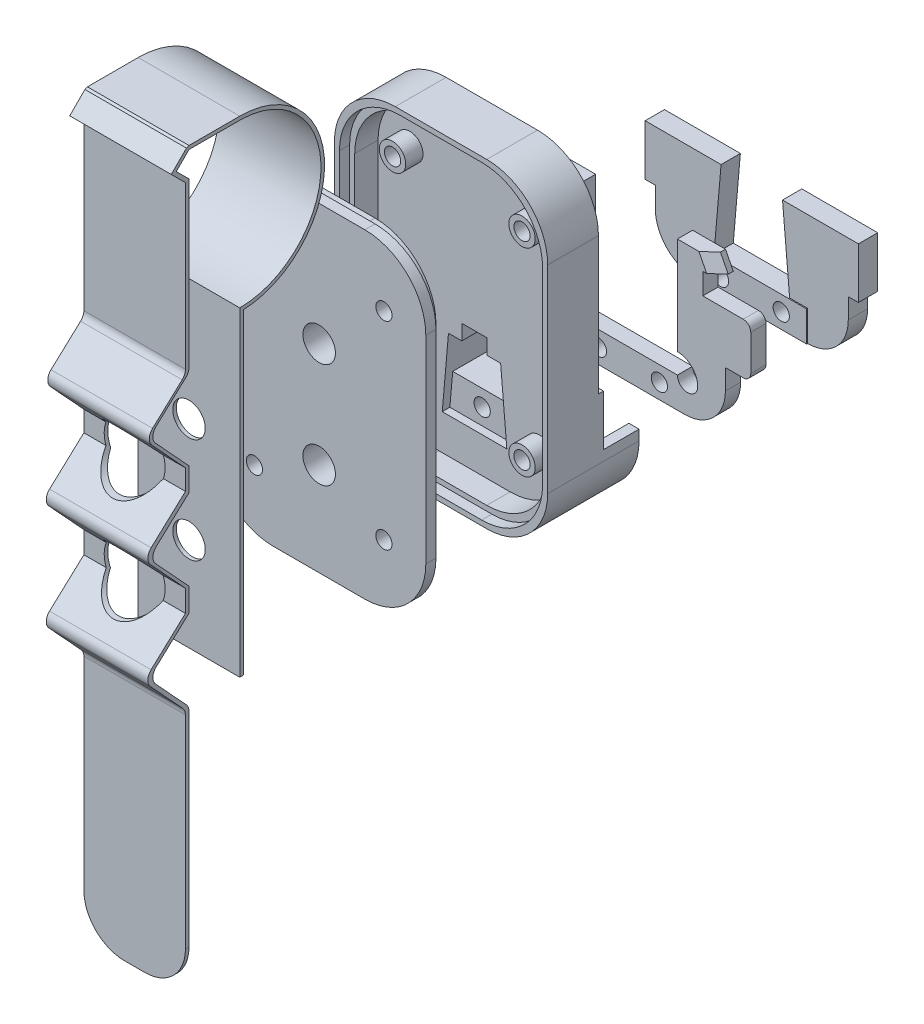
SolidWorks part; units mm, degrees
ref_plane "前视基准面" through (0, 0, 0) normal (0, 0, 1) x (1, 0, 0)
ref_plane "上视基准面" through (0, 0, 0) normal (0, 1, 0) x (1, 0, 0)
ref_plane "右视基准面" through (0, 0, 0) normal (1, 0, 0) x (0, 0, -1)
sketch "草图2" plane through (0, 0, 0) normal (0, 0, 1) x (1, 0, 0)
  line L1 (-21, 31.5) -> (21, 31.5)
  line L2 (-21, 31.5) -> (-21, -31.5)
  line L3 (-21, -31.5) -> (21, -31.5)
  line L4 (21, 31.5) -> (21, -31.5)
  line L5 (-21, 31.5) -> (21, -31.5) construction
  line L6 (-21, -31.5) -> (21, 31.5) construction
  point P0 (0, 0)
extrude "凸台-拉伸1" add sketch "草图2" along normal blind 10
sketch "草图3" plane through (0, 0, 0) normal (0, 0, -1) x (-1, 0, 0)
  line L0 (21, 31.5) -> (21, -31.5) construction
  line L1 (-21, -31.5) -> (21, -31.5)
  line L2 (-21, -31.5) -> (-21, -7.5)
  line L3 (-21, -7.5) -> (21, -7.5)
  line L4 (21, -31.5) -> (21, -7.5)
extrude "凸台-拉伸2" add sketch "草图3" along normal blind 8
sketch "草图4" plane through (0, -7.5, 0) normal (0, 1, 0) x (1, 0, 0)
  line L0 (0, 0) -> (0, 3)
  line L1 (0, 3) -> (5.5, 3)
  line L2 (0, 3) -> (-5.5, 3)
  line L3 (5.5, 3) -> (3.5, 0)
  line L4 (21, 0) -> (-21, 0) construction
  line L5 (-5.5, 3) -> (-3.5, 0)
  line L6 (0, 0) -> (3.5, 0)
  line L7 (0, 0) -> (-3.5, 0)
  line M4 (-21, 0) -> (21, 0)
  dimension "D1" = 3
extrude "凸台-拉伸3" add sketch "草图4" along normal blind 32 contours L2 L5 L0 M4 | L3 L1 L0 M4 region at (-2.287, -7.5, -1.6111) region at (2.287, -7.5, -1.6111)
sketch "草图5" plane through (0, -7.5, 0) normal (0, 1, 0) x (1, 0, 0)
  line L0 (0, 6.25) -> (0, 0)
  line L1 (-3.81, 6.25) -> (3.81, 6.25)
  line L3 (-5.05, 5) -> (5.05, 5)
  line L4 (-5.05, 5) -> (-5.05, 7.5)
  line L5 (-5.05, 7.5) -> (5.05, 7.5)
  line L6 (5.05, 5) -> (5.05, 7.5)
  line L7 (-5.05, 5) -> (5.05, 7.5) construction
  line L8 (-5.05, 7.5) -> (5.05, 5) construction
  circle A0 centre (1.27, 6.25) radius 0.74
  circle A1 centre (3.81, 6.25) radius 0.74
  circle A2 centre (-1.27, 6.25) radius 0.74
  circle A3 centre (-3.81, 6.25) radius 0.74
  point P2 (0, 6.25)
  point P5 (0, 6.25)
  dimension "D4" = 1.48
  dimension "D2" = 10.1
  dimension "D5" = 2
  dimension "D6" = 3
extrude "切除-拉伸1" cut sketch "草图5" against normal blind 10 contours A3 | A2 | A0 | A1 | A2 | A0 region at (-4.5291, -7.5, -6.25) region at (-1.27, -7.5, -5.9359) region at (3.81, -7.5, -6.9691) region at (1.27, -7.5, -5.9359)
fillet "圆角1" radius 3 2 edges at (-4.5, 24.5, -1.5) (4.5, 24.5, -1.5)
sketch "草图6" plane through (0, 0, -8) normal (0, 0, -1) x (-1, 0, 0)
  line L0 (-21, -7.5) -> (-17.55, -7.5)
  line L1 (-3.5, -7.5) -> (-21, -7.5) construction
  line L2 (21, -7.5) -> (17.55, -7.5)
  line L3 (21, -7.5) -> (3.5, -7.5) construction
  line L4 (-17.55, -7.5) -> (-14.55, -7.5)
  line L5 (17.55, -7.5) -> (14.55, -7.5)
  line L6 (21, -7.5) -> (-21, -7.5) construction
  line L7 (-14.55, -7.5) -> (-9.55, -7.5)
  line L8 (14.55, -7.5) -> (9.55, -7.5)
  line L9 (-9.55, -7.5) -> (-7.55, -7.5)
  line L10 (9.55, -7.5) -> (7.55, -7.5)
  line L11 (-21, -31.5) -> (21, -31.5) construction
  line L12 (-21, -7.5) -> (-9.55, -7.5)
  line L13 (-21, -7.5) -> (-21, -17.5)
  line L15 (-9.55, -7.5) -> (-9.55, -19.5)
  line L16 (-21, -17.5) -> (-19, -17.5)
  line L17 (-21, -17.5) -> (-21, -31.5)
  line L19 (-19, -17.5) -> (-19, -21.5)
  line L20 (-21, -17.5) -> (-21, -7.5)
  line L22 (-9.55, -31.5) -> (-9.55, -29.5)
  line L23 (-9.55, -29.5) -> (-11, -29.5)
  line L25 (-9.55, -29.5) -> (0, -29.5)
  line L27 (-9.55, -23.5) -> (0, -23.5)
  line L29 (9.55, -29.5) -> (11, -29.5)
  line L30 (0, -23.5) -> (9.55, -23.5)
  line L32 (0, -29.5) -> (9.55, -29.5)
  line L34 (19, -21.5) -> (19, -17.5)
  line L35 (21, -31.5) -> (21, -7.5) construction
  line L36 (19, -17.5) -> (21, -17.5)
  line L37 (9.55, -19.5) -> (9.55, -7.5)
  line L38 (9.55, -29.5) -> (9.55, -31.5)
  line L39 (21, -7.5) -> (21, -17.5)
  line L40 (-21, -7.5) -> (-21, -17.5)
  arc A0 (-11, -29.5) -> (-19, -21.5) centre (-11, -21.5) cw
  arc A1 (-9.55, -19.5) -> (-13.55, -23.5) centre (-9.55, -23.5) ccw
  arc A2 (-13.55, -23.5) -> (-9.55, -23.5) centre (-11.55, -23.5) ccw
  arc A3 (11, -29.5) -> (19, -21.5) centre (11, -21.5) ccw
  arc A4 (9.55, -23.5) -> (13.55, -23.5) centre (11.55, -23.5) ccw
  arc A5 (13.55, -23.5) -> (9.55, -19.5) centre (9.55, -23.5) ccw
  line M7 (-21, -7.5) -> (-21, -31.5)
  line M9 (21, -31.5) -> (21, -7.5)
  line M10 (21, -7.5) -> (-21, -7.5)
  dimension "D7" = 8
  dimension "D8" = 2
  dimension "D9" = 2
  dimension "D10" = 2
  dimension "D11" = 4
  dimension "D12" = 4
  dimension "D13" = 10
  dimension "D1" = 3.45
  dimension "D2" = 3
  dimension "D3" = 5
  dimension "D4" = 2
  dimension "D5" = 2
  dimension "D6" = 2
  dimension "D14" = 10
extrude "切除-拉伸2" cut sketch "草图6" against normal blind 7 contours A5 A4 L30 L27 A2 A1 L15 L16 L19 A0 L23 L25 L32 L29 A3 L34 L36 L37 M10 M7 M9 region at (19.275, -7.9741, -8)
sketch "草图7" plane through (0, 0, -8) normal (0, 0, -1) x (-1, 0, 0)
  line L0 (-9.55, -7.5) -> (-7.55, -7.5)
  line L1 (9.55, -7.5) -> (-9.55, -7.5) construction
  line L2 (9.55, -7.5) -> (7.55, -7.5)
  line L4 (-7.55, -7.5) -> (-13.55, -7.5)
  line L5 (-7.55, -7.5) -> (-7.55, -25.5)
  line L6 (-7.55, -25.5) -> (-13.55, -25.5)
  line L7 (-13.55, -7.5) -> (-13.55, -25.5)
  line L8 (7.55, -7.5) -> (13.55, -7.5)
  line L9 (7.55, -7.5) -> (7.55, -25.5)
  line L10 (7.55, -25.5) -> (13.55, -25.5)
  line L11 (13.55, -7.5) -> (13.55, -25.5)
  line M3 (9.55, -19.5) -> (9.55, -7.5)
  line M4 (9.55, -7.5) -> (-9.55, -7.5)
  line M5 (-9.55, -7.5) -> (-9.55, -19.5)
  arc M6 (-9.55, -19.5) -> (-13.55, -23.5) centre (-9.55, -23.5) ccw
  arc M7 (-13.55, -23.5) -> (-9.55, -23.5) centre (-11.55, -23.5) ccw
  line M8 (-9.55, -23.5) -> (9.55, -23.5)
  arc M9 (9.55, -23.5) -> (13.55, -23.5) centre (11.55, -23.5) ccw
  arc M10 (13.55, -23.5) -> (9.55, -19.5) centre (9.55, -23.5) ccw
  dimension "D1" = 2
extrude "切除-拉伸3" cut sketch "草图7" against normal blind 7 contours L5 M4 M5 M6 M7 M8 | L9 M4 M8 M9 M10 M3 region at (8.55, -7.6897, -8) region at (-8.55, -7.6897, -8)
sketch "草图8" plane through (0, 0, -1) normal (0, 0, -1) x (-1, 0, 0)
  line L0 (0, -26.5) -> (6, -26.5)
  line L1 (11, -29.5) -> (-11, -29.5) construction
  line L2 (0, -29.5) -> (0, -23.5)
  line L3 (-7.55, -23.5) -> (7.55, -23.5) construction
  line L4 (0, -26.5) -> (-6, -26.5)
  circle A0 centre (-6, -26.5) radius 1.6
  circle A1 centre (6, -26.5) radius 1.6
  dimension "D1" = 6
extrude "切除-拉伸4" cut sketch "草图8" against normal blind 3 contours A1 | A0 region at (-6, -24.9453, -1)
fillet "圆角6" radius 12 4 edges at (21, -31.5, 1) (-21, -31.5, 1) (-21, 31.5, 5) (21, 31.5, 5)
sketch "草图10" plane through (0, 0, 0) normal (0, 0, 1) x (1, 0, 0)
  line L0 (-21, -7.5) -> (-17.55, -7.5)
  line L1 (-21, -7.5) -> (-24, -7.5)
  line L2 (21, -7.5) -> (17.55, -7.5)
  line L3 (-24, -7.5) -> (-24, -17.5)
  line L4 (-17.55, -7.5) -> (-14.55, -7.5)
  line L5 (17.55, -7.5) -> (14.55, -7.5)
  line L6 (-24, -17.5) -> (-21, -17.5)
  line L7 (-14.55, -7.5) -> (-9.55, -7.5)
  line L8 (14.55, -7.5) -> (9.55, -7.5)
  line L9 (-9.55, -7.5) -> (-7.55, -7.5)
  line L10 (9.55, -7.5) -> (7.55, -7.5)
  line L11 (21, -7.5) -> (24, -7.5)
  line L12 (-21, -7.5) -> (-9.55, -7.5)
  line L13 (-21, -7.5) -> (-21, -17.5)
  line L15 (-9.55, -7.5) -> (-9.55, -19.5)
  line L16 (-21, -17.5) -> (-19, -17.5)
  line L17 (-21, -17.5) -> (-21, -31.5)
  line L19 (-19, -17.5) -> (-19, -21.5)
  line L20 (-21, -17.5) -> (-21, -7.5)
  line L22 (-9.55, -31.5) -> (-9.55, -29.5)
  line L23 (-9.55, -29.5) -> (-11, -29.5)
  line L25 (-9.55, -29.5) -> (0, -29.5)
  line L27 (-9.55, -23.5) -> (0, -23.5)
  line L29 (9.55, -29.5) -> (11, -29.5)
  line L30 (0, -23.5) -> (9.55, -23.5)
  line L32 (0, -29.5) -> (9.55, -29.5)
  line L34 (19, -21.5) -> (19, -17.5)
  line L35 (24, -7.5) -> (24, -17.5)
  line L36 (19, -17.5) -> (21, -17.5)
  line L37 (9.55, -19.5) -> (9.55, -7.5)
  line L38 (9.55, -29.5) -> (9.55, -31.5)
  line L39 (21, -7.5) -> (21, -17.5)
  line L40 (-21, -7.5) -> (-21, -17.5)
  line L41 (9.55, -7.5) -> (9.55, -0.3)
  line L42 (16.031, -0.3) -> (17.55, -3.3)
  line L43 (17.55, -3.3) -> (14.55, -3.3)
  line L44 (14.55, -3.3) -> (14.55, -7.5)
  line L45 (-9.55, -7.5) -> (-9.55, -0.3)
  line L46 (-16.031, -0.3) -> (-17.55, -3.3)
  line L47 (-17.55, -3.3) -> (-14.55, -3.3)
  line L48 (-14.55, -3.3) -> (-14.55, -7.5)
  line L49 (24, -17.5) -> (21, -17.5)
  line L50 (9.55, -3.3) -> (14.55, -3.3)
  line L51 (-14.55, -3.3) -> (-9.55, -3.3)
  line L53 (9.55, -0.3) -> (16.031, -0.3)
  line L54 (-9.55, -0.3) -> (-16.031, -0.3)
  arc A0 (-11, -29.5) -> (-19, -21.5) centre (-11, -21.5) cw
  arc A1 (-9.55, -19.5) -> (-13.55, -23.5) centre (-9.55, -23.5) ccw
  arc A2 (-13.55, -23.5) -> (-9.55, -23.5) centre (-11.55, -23.5) ccw
  arc A3 (11, -29.5) -> (19, -21.5) centre (11, -21.5) ccw
  arc A4 (9.55, -23.5) -> (13.55, -23.5) centre (11.55, -23.5) ccw
  arc A5 (13.55, -23.5) -> (9.55, -19.5) centre (9.55, -23.5) ccw
  circle A6 centre (6, -26.5) radius 1.6
  circle A7 centre (-6, -26.5) radius 1.6
  dimension "D7" = 8
  dimension "D9" = 2
  dimension "D10" = 2
  dimension "D11" = 4
  dimension "D12" = 4
  dimension "D13" = 10
  dimension "D1" = 3.45
  dimension "D2" = 3
  dimension "D3" = 5
  dimension "D4" = 2
  dimension "D5" = 2
  dimension "D6" = 12
  dimension "D14" = 10
extrude "弹性件" add sketch "草图10" along normal blind 3 from offset 30 separate body contours L44 L43 L42 L41 L8 | L47 L48 L7 L45 L46 | L13 L1 L3 L6 | L49 L35 L11 L39 | A5 A4 L30 L27 A2 A1 L15 L7 L4 L0 L13 L16 L19 A0 L23 L25 L32 L29 A3 L34 L36 L39 L2 L5 L8 L37 A7 A6 | L51 L48 L7 L45 | L50 L41 L8 L44 region at (-22.5, -12.5, 0) region at (-19.275, -7.9741, 0) region at (-12.05, -5.4, 0) region at (-13.1835, -1.8524, 0) region at (12.05, -5.4, 0) region at (22.5, -12.5, 0) region at (13.1835, -1.8524, 0) offset against normal yes
fillet "圆角2" radius 1.5 4 edges at (24, -17.5, -28.5) (24, -7.5, -28.5) (-24, -17.5, -28.5) (-24, -7.5, -28.5)
sketch "草图11" plane through (0, 0, -1) normal (0, 0, -1) x (-1, 0, 0)
  line L5 (-11, -29.5) -> (11, -29.5)
  line L6 (-11, -29.5) -> (-11, -23.5)
  line L7 (-11, -23.5) -> (11, -23.5)
  line L8 (11, -29.5) -> (11, -23.5)
extrude "凸台-拉伸6" add sketch "草图11" along normal blind 0.2 from offset 50 separate body
sketch "草图12" plane through (0, 0, -51.2) normal (0, 0, -1) x (-1, 0, 0)
  line L1 (11, -23.5) -> (-11, -23.5) construction
  line L2 (-11, -29.5) -> (11, -29.5)
  line L3 (-21, -17.5) -> (-21, -7.5)
  line L4 (-21, -7.5) -> (-7.55, -7.5)
  line L5 (-7.55, -7.5) -> (-7.55, -14.2821)
  line L6 (-7.55, -7.5) -> (-7.55, -23.5) construction
  line L7 (7.55, -7.5) -> (21, -7.5)
  line L8 (21, -7.5) -> (21, -17.5)
  line L9 (21, -17.5) -> (19, -17.5)
  line L10 (19, -17.5) -> (19, -21.5)
  line L11 (-21, -17.5) -> (-19, -17.5)
  line L12 (-19, -17.5) -> (-19, -21.5)
  line L13 (7.55, -7.5) -> (7.55, -23.5)
  line L14 (-7.55, -14.2821) -> (-7.55, -23.5)
  arc A1 (-19, -21.5) -> (-11, -29.5) centre (-11, -21.5) ccw
  circle A2 centre (-6, -26.5) radius 1.6
  circle A4 centre (6, -26.5) radius 1.6465
  arc A5 (11, -29.5) -> (19, -21.5) centre (11, -21.5) ccw
  line M3 (-11, -23.5) -> (-11, -29.5)
  line M4 (-11, -29.5) -> (11, -29.5)
  line M5 (11, -29.5) -> (11, -23.5)
  line M6 (11, -23.5) -> (-11, -23.5)
extrude "凸台-拉伸7" add sketch "草图12" along normal blind 3.8 contours L12 A1 L14 L5 L4 L3 L11 M3 M6 | A4 A2 M6 M3 M4 M5 | A5 L10 L9 L8 L7 L13 M5 M6 region at (0.0246, -26.5, -51.2) region at (13.9623, -16.7644, -51.2) region at (-13.9623, -16.7644, -51.2)
chamfer "倒角2" distance 1 angle 45 2 edges at (-7.6465, -26.5, -55) (4.4, -26.5, -55)
sketch "草图25" plane through (0, 0, -55) normal (0, 0, -1) x (-1, 0, 0)
  circle A0 centre (6, -26.5) radius 1.6465
  circle A1 centre (-6, -26.5) radius 1.6
extrude "切除-拉伸12" cut sketch "草图25" against normal blind 4.2
chamfer "底座缝隙件" distance 1.5 angle 85 2 edges at (7.55, -7.5, -4.5) (-7.55, -7.5, -4.5) first distance on face at (-1.27, -7.5, -5.51)
sketch "草图13" plane through (0, 0, -55) normal (0, 0, -1) x (-1, 0, 0)
  line L0 (-6.05, -7.5) -> (-7.4498, -23.5)
  line L1 (-7.4498, -23.5) -> (-7.55, -23.5)
  line L2 (-7.55, -23.5) -> (-7.55, -7.5)
  line L3 (-7.55, -7.5) -> (-6.05, -7.5)
  line L4 (6.05, -7.5) -> (7.55, -7.5)
  line L5 (7.55, -7.5) -> (7.55, -23.5)
  line L6 (7.55, -23.5) -> (7.4498, -23.5)
  line L7 (7.4498, -23.5) -> (6.05, -7.5)
extrude "盖板缝隙件" add sketch "草图13" against normal blind 3.8
sketch "草图14" plane through (0, 0, 10) normal (0, 0, 1) x (1, 0, 0)
  line L0 (21, -19.5) -> (21, 19.5) construction
  line L1 (-7, -29.5) -> (7, -29.5)
  line L2 (-19, -17.5) -> (-19, 17.5)
  line L3 (-7, 29.5) -> (7, 29.5)
  line L4 (19, -17.5) -> (19, 17.5)
  line L5 (-19, -29.5) -> (19, 29.5) construction
  line L6 (-19, 29.5) -> (19, -29.5) construction
  line L7 (9, 31.5) -> (-9, 31.5) construction
  arc A0 (-7, -29.5) -> (-19, -17.5) centre (-7, -17.5) cw
  arc A1 (7, -29.5) -> (19, -17.5) centre (7, -17.5) ccw
  arc A2 (7, 29.5) -> (19, 17.5) centre (7, 17.5) cw
  arc A3 (-19, 17.5) -> (-7, 29.5) centre (-7, 17.5) cw
  point P0 (0, 0)
  dimension "D3" = 12
  dimension "D1" = 2
  dimension "D2" = 2
extrude "切除-拉伸5" cut sketch "草图14" against normal blind 6.6
sketch "草图15" plane through (0, 0, 10) normal (0, 0, 1) x (1, 0, 0)
  line L0 (7, 29.5) -> (-7, 29.5) construction
  line L1 (-8, -30.5) -> (8, -30.5)
  line L2 (-20, -18.5) -> (-20, 18.5)
  line L3 (-8, 30.5) -> (8, 30.5)
  line L4 (20, -18.5) -> (20, 18.5)
  line L5 (-20, -30.5) -> (20, 30.5) construction
  line L6 (-20, 30.5) -> (20, -30.5) construction
  line L7 (19, -17.5) -> (19, 17.5) construction
  line L8 (9, 31.5) -> (-9, 31.5) construction
  arc A0 (-8, -30.5) -> (-20, -18.5) centre (-8, -18.5) cw
  arc A1 (8, -30.5) -> (20, -18.5) centre (8, -18.5) ccw
  arc A2 (8, 30.5) -> (20, 18.5) centre (8, 18.5) cw
  arc A3 (-20, 18.5) -> (-8, 30.5) centre (-8, 18.5) cw
  point P0 (0, 0)
  dimension "D3" = 12
  dimension "D1" = 1
  dimension "D2" = 1
  dimension "D4" = 1
extrude "切除-拉伸6" cut sketch "草图15" against normal blind 2
sketch "草图16" plane through (0, 0, 10) normal (0, 0, 1) x (1, 0, 0)
  line L1 (-21, -31.5) -> (21, -31.5)
  line L2 (-21, -31.5) -> (-21, 31.5)
  line L3 (-21, 31.5) -> (21, 31.5)
  line L4 (21, -31.5) -> (21, 31.5)
  line L5 (-21, -31.5) -> (21, 31.5) construction
  line L6 (-21, 31.5) -> (21, -31.5) construction
  point P0 (0, 0)
extrude "凸台-拉伸9" add sketch "草图16" along normal blind 4 from offset 20
sketch "草图19" plane through (0, 0, 30) normal (0, 0, -1) x (-1, 0, 0)
  line L0 (21, 31.5) -> (21, -31.5) construction
  line L1 (-6, -28.5) -> (6, -28.5)
  line L2 (-18, -16.5) -> (-18, 16.5)
  line L3 (-6, 28.5) -> (6, 28.5)
  line L4 (18, -16.5) -> (18, 16.5)
  line L5 (-18, -28.5) -> (18, 28.5) construction
  line L6 (-18, 28.5) -> (18, -28.5) construction
  line L7 (-21, 31.5) -> (21, 31.5) construction
  arc A0 (6, -28.5) -> (18, -16.5) centre (6, -16.5) ccw
  arc A1 (-6, -28.5) -> (-18, -16.5) centre (-6, -16.5) cw
  arc A2 (6, 28.5) -> (18, 16.5) centre (6, 16.5) cw
  arc A3 (-18, 16.5) -> (-6, 28.5) centre (-6, 16.5) cw
  point P0 (0, 0)
  dimension "D3" = 12
  dimension "D1" = 3
  dimension "D2" = 3
extrude "凸台-拉伸10" add sketch "草图19" along normal blind 1
sketch "草图20" plane through (0, 0, 30) normal (0, 0, -1) x (-1, 0, 0)
  line L0 (21, 31.5) -> (21, -31.5) construction
  line L1 (-7, -30.5) -> (7, -30.5)
  line L2 (-19, -18.5) -> (-19, 18.5)
  line L3 (-7, 30.5) -> (7, 30.5)
  line L4 (19, -18.5) -> (19, 18.5)
  line L5 (-19, -30.5) -> (19, 30.5) construction
  line L6 (-19, 30.5) -> (19, -30.5) construction
  line L7 (-21, 31.5) -> (21, 31.5) construction
  line L9 (21, -31.5) -> (-21, -31.5)
  line L10 (21, -31.5) -> (21, 31.5)
  line L11 (21, 31.5) -> (-21, 31.5)
  line L12 (-21, -31.5) -> (-21, 31.5)
  line L13 (21, -31.5) -> (-21, 31.5) construction
  line L14 (21, 31.5) -> (-21, -31.5) construction
  arc A0 (-7, -30.5) -> (-19, -18.5) centre (-7, -18.5) cw
  arc A1 (7, -30.5) -> (19, -18.5) centre (7, -18.5) ccw
  arc A2 (-19, 18.5) -> (-7, 30.5) centre (-7, 18.5) cw
  arc A3 (7, 30.5) -> (19, 18.5) centre (7, 18.5) cw
  point P0 (0, 0)
  point P22 (0, 0)
  dimension "D3" = 12
  dimension "D2" = 1
  dimension "1" = 2
extrude "切除-拉伸7" cut sketch "草图20" against normal blind 2
sketch "草图21" plane through (0, 0, 0) normal (1, 0, 0) x (0, 0, -1)
  line L0 (-59.6372, -31.5) -> (-59.6372, 31.5)
  line L1 (-59.6372, 63.5) -> (-69.6372, 63.5)
  line L2 (-58.9372, 63.4847) -> (-59.6372, 63.5)
  line L3 (-58.9372, -31.5) -> (-58.9372, 31.5) construction
  line L4 (-69.6372, 25.5) -> (-77.5793, 18.179)
  line L5 (-77.5793, 18.179) -> (-69.6372, 9.5631)
  line L6 (-69.6372, 9.5631) -> (-69.6372, 4.9685)
  line L7 (-69.6372, -10.9685) -> (-69.6372, -15.5631)
  line L8 (-69.6372, 4.9685) -> (-77.5793, -2.3525)
  line L9 (-77.5793, -2.3525) -> (-69.6372, -10.9685)
  line L10 (-69.6372, -15.5631) -> (-77.5793, -22.884)
  line L11 (-69.6372, 63.5) -> (-72.1372, 61)
  line L12 (-69.6372, 58.5) -> (-69.6372, 25.5)
  line L13 (-72.1372, 61) -> (-69.6372, 58.5)
  line L14 (-77.5793, -22.884) -> (-69.6372, -31.5)
  line L15 (-69.6372, 25.5) -> (-69.6372, -10.9685)
  line L16 (-69.6372, -15.5631) -> (-69.6372, -31.5)
  line L17 (-69.6372, -31.5) -> (-69.6372, -80.5)
  line L18 (-58.9372, -31.5) -> (-58.9372, 30.8147)
  line L19 (-59.6372, 64.2) -> (-69.6372, 64.2)
  line L20 (-58.9372, 63.4847) -> (-58.9372, 63.5)
  line L21 (-58.9372, 31.5) -> (-58.9372, 31.5153)
  line L22 (-70.3372, -10.9685) -> (-70.3372, -15.2563)
  line L23 (-70.3372, -15.2563) -> (-78.5685, -22.8438)
  line L24 (-78.5685, -22.8438) -> (-70.3372, -31.7734)
  line L25 (-70.1322, 63.995) -> (-73.1272, 61)
  line L26 (-73.1272, 61) -> (-70.3372, 58.2101)
  line L27 (-70.3372, 58.2101) -> (-70.3372, 25.5)
  line L29 (-70.3372, -31.7734) -> (-70.3372, -80.5)
  line L30 (-70.1322, 63.995) -> (-69.6372, 64.2)
  line L31 (-73.1272, 61) -> (-70.1322, 58.005) construction
  line L33 (-70.3372, 58.5) -> (-70.3372, 25.5) construction
  line L34 (-78.5685, -22.8438) -> (-70.1519, -31.9744) construction
  line L35 (-70.3372, -31.5) -> (-70.3372, -80.5) construction
  line L36 (-70.1117, -15.0484) -> (-78.5685, -22.8438) construction
  line L37 (-70.3372, -10.9685) -> (-70.3372, -15.5631) construction
  line L38 (-70.3372, -10.9685) -> (-78.5685, -2.0388)
  line L39 (-78.5685, -2.0388) -> (-70.3372, 5.5486)
  line L40 (-70.3372, 5.5486) -> (-70.3372, 9.5631)
  line L41 (-70.3372, 9.5631) -> (-78.2793, 18.179)
  line L42 (-78.2793, 18.179) -> (-70.3372, 25.5)
  line L43 (-59.6372, -31.5) -> (-58.9372, -31.5)
  line L44 (-69.6372, -80.5) -> (-70.3372, -80.5)
  arc A0 (-59.6372, 31.5) -> (-58.9372, 63.4847) centre (-59.6372, 47.5) ccw
  arc A1 (-58.9372, 30.8147) -> (-59.6372, 64.2) centre (-59.6372, 47.5) ccw
  arc A2 (-59.6372, 31.5) -> (-59.6372, 63.5) centre (-59.6372, 47.5) ccw construction
  arc A3 (-59.6372, 30.8) -> (-59.6372, 64.2) centre (-59.6372, 47.5) ccw construction
  dimension "D1" = 16
  dimension "D2" = 10
  dimension "D3" = 38
  dimension "D4" = 0.7
extrude "凸台-拉伸11" add sketch "草图21" along normal blind 10 and the other way blind 10 separate body contours L18 A1 L19 L30 L25 L26 L27 L42 L41 L40 L39 L38 L22 L23 L24 L29 L44 L17 L14 L10 L7 L9 L8 L6 L5 L4 L12 L13 L11 L1 L2 A0 L0 L43 region at (0, 0, 59.4882)
fillet "圆角3" radius 2 3 edges at (0, -22.884, 77.5793) (0, -2.3525, 77.5793) (0, 18.179, 77.5793)
fillet "圆角4" radius 2 7 edges at (0, 25.5, 70.3372) (0, -31.7734, 70.3372) (0, -31.5, 69.6372) (0, 25.5, 69.6372) (0, -22.8438, 78.5685) (0, -2.0388, 78.5685) (0, 18.179, 78.2793)
sketch "草图22" plane through (0, 0, 70.3372) normal (0, 0, 1) x (1, 0, 0)
  line L0 (0, 9.5631) -> (0, 5.5486)
  line L1 (-10, 9.5631) -> (10, 9.5631) construction
  line L2 (-10, 5.5486) -> (10, 5.5486) construction
  line L3 (0, -10.9685) -> (0, -15.2563)
  line L4 (-10, -10.9685) -> (10, -10.9685) construction
  line L5 (-10, -15.2563) -> (10, -15.2563) construction
  circle A0 centre (0, 7.5559) radius 6
  circle A1 centre (0, -13.1124) radius 6
  line M3 (-10, 5.5486) -> (10, 5.5486)
  line M5 (10, 9.5631) -> (-10, 9.5631)
extrude "切除-拉伸8" cut sketch "草图22" against normal blind 8 and the other way blind 12 contours A0 M5 | A0 L0 M5 M3 | A0 L0 M3 M5 | A0 M3 | A1 region at (2.944, 7.5559, 70.3372) region at (0, 11.2168, 70.3372) region at (-2.944, 7.5559, 70.3372) region at (0, 3.8949, 70.3372) region at (-5.8303, -13.1124, 70.3372)
sketch "草图23" plane through (0, 0, 59.6372) normal (0, 0, 1) x (1, 0, 0)
  circle A0 centre (0, 7.5559) radius 3.2
  circle A1 centre (0, -13.1124) radius 3.2
extrude "切除-拉伸10" cut sketch "草图23" against normal blind 0.7
sketch "草图24" plane through (0, 0, 34) normal (0, 0, 1) x (1, 0, 0)
  circle A0 centre (0, 7.5559) radius 3.2
  circle A1 centre (0, -13.1124) radius 3.2
extrude "切除-拉伸11" cut sketch "草图24" against normal blind 6
fillet "圆角5" radius 8 2 edges at (10, -80.5, 69.9872) (-10, -80.5, 69.9872)
fillet "圆角7" radius 12 4 edges at (21, -31.5, 33) (-21, -31.5, 33) (-21, 31.5, 33) (21, 31.5, 33)
sketch "草图27" plane through (0, 0, 34) normal (0, 0, 1) x (1, 0, 0)
  line L0 (-15.5, -19.5) -> (-10, -19.5)
  line L1 (-10, -15.2563) -> (-10, -21.4882) construction
  line L2 (15.5, -19.5) -> (10, -19.5)
  line L3 (10, -15.2563) -> (10, -21.4882) construction
  line L4 (-15.5, 19.5173) -> (-10, 19.5346)
  line L5 (15.5, 19.5173) -> (10, 19.5346)
  circle A0 centre (-12.75, 19.5259) radius 1.6
  circle A1 centre (12.75, 19.5259) radius 1.6
  circle A2 centre (12.75, -19.5) radius 1.6
  circle A3 centre (-12.75, -19.5) radius 1.6
extrude "切除-拉伸13" cut sketch "草图27" against normal blind 6 contours A0 | A2 | A3 | A1
sketch "草图28" plane through (0, 0, 3.4) normal (0, 0, 1) x (1, 0, 0)
  circle A0 centre (-12.75, 19.5259) radius 1.6
  circle A1 centre (12.75, 19.5259) radius 1.6
  circle A2 centre (12.75, -19.5) radius 1.6
  circle A3 centre (-12.75, -19.5) radius 1.6
extrude "切除-拉伸14" cut sketch "草图28" against normal blind 2
sketch "草图29" plane through (0, 0, 3.4) normal (0, 0, 1) x (1, 0, 0)
  circle A0 centre (12.75, 19.5259) radius 2.6
  circle A1 centre (-12.75, 19.5259) radius 2.6
  circle A2 centre (-12.75, -19.5) radius 2.6
  circle A3 centre (12.75, -19.5) radius 2.6
extrude "凸台-拉伸12" add sketch "草图29" along normal blind 3.4
sketch "草图32" plane through (0, 0, 6.8) normal (0, 0, 1) x (1, 0, 0)
  circle A0 centre (-12.75, 19.5259) radius 1.6
  circle A1 centre (12.75, 19.5259) radius 1.6
  circle A2 centre (12.75, -19.5) radius 1.6
  circle A3 centre (-12.75, -19.5) radius 1.6
extrude "切除-拉伸16" cut sketch "草图32" against normal blind 2.4
chamfer "倒角3" distance 2 angle 45 2 edges at (16.7905, -1.8, -27) (-16.7905, -1.8, -27)
sketch "草图35" plane through (0, 0, -8) normal (0, 0, -1) x (-1, 0, 0)
  line L0 (-6.05, -7.5) -> (-7.4498, -23.5)
  line L1 (-7.4498, -23.5) -> (7.4498, -23.5)
  line L2 (7.4498, -23.5) -> (6.05, -7.5)
  line L3 (6.05, -7.5) -> (-6.05, -7.5)
extrude "凸台-拉伸13" add sketch "草图35" along normal blind 1
sketch "草图36" plane through (0, 0, 3.4) normal (0, 0, 1) x (1, 0, 0)
  line L0 (6.05, -7.5) -> (-6.05, -7.5)
  line L1 (-6.05, -7.5) -> (-7.4498, -23.5)
  line L2 (-7.4498, -23.5) -> (7.4498, -23.5)
  line L3 (7.4498, -23.5) -> (6.05, -7.5)
  line L4 (6.3585, -22.5) -> (5.1337, -8.5)
  line L5 (5.1337, -8.5) -> (-5.1337, -8.5)
  line L6 (-5.1337, -8.5) -> (-6.3585, -22.5)
  line L7 (-6.3585, -22.5) -> (6.3585, -22.5)
  line L8 (0, -8.5) -> (0, -18.7)
  line L9 (6.0261, -18.7) -> (-6.0261, -18.7)
  dimension "D1" = 1
  dimension "D2" = 10.2
extrude "切除-拉伸17" cut sketch "草图36" against normal blind 11.5 contours L4 L5 L6 L7
sketch "草图38" plane through (0, -8.5, 0) normal (0, -1, 0) x (-1, 0, 0)
  line L0 (2.5, -3.4) -> (-2.5, -3.4)
  line L1 (-5.1337, -3.4) -> (5.1337, -3.4) construction
  line L2 (2.5, -3.4) -> (2.5, 1.6)
  line L3 (2.5, 1.6) -> (-2.5, 1.6)
  line L4 (-2.5, 1.6) -> (-2.5, -3.4)
  point P5 (0, -3.4)
extrude "切除-拉伸19" cut sketch "草图38" against normal blind 3
sketch "草图39" plane through (0, 0, -8.1) normal (0, 0, 1) x (1, 0, 0)
  line L2 (0, -16.1) -> (5.7986, -16.1)
  line L3 (6.3585, -22.5) -> (5.1337, -8.5) construction
  line L4 (0, -16.1) -> (-5.7986, -16.1)
  line L5 (-5.1337, -8.5) -> (-6.3585, -22.5) construction
  line L6 (5.7986, -16.1) -> (6.3585, -22.5)
  line L7 (6.3585, -22.5) -> (-6.3585, -22.5)
  line L8 (-6.3585, -22.5) -> (-5.7986, -16.1)
extrude "凸台-拉伸15" add sketch "草图39" along normal blind 10
sketch "草图40" plane through (0, 0, 1.9) normal (0, 0, 1) x (1, 0, 0)
  line L0 (0, -16.1) -> (0, -22.5)
  line L1 (5.7986, -16.1) -> (-5.7986, -16.1) construction
  line L2 (-6.3585, -22.5) -> (6.3585, -22.5) construction
  circle A0 centre (0, -19.3) radius 1.6
extrude "切除-拉伸20" cut sketch "草图40" against normal blind 10.4 contours A0
